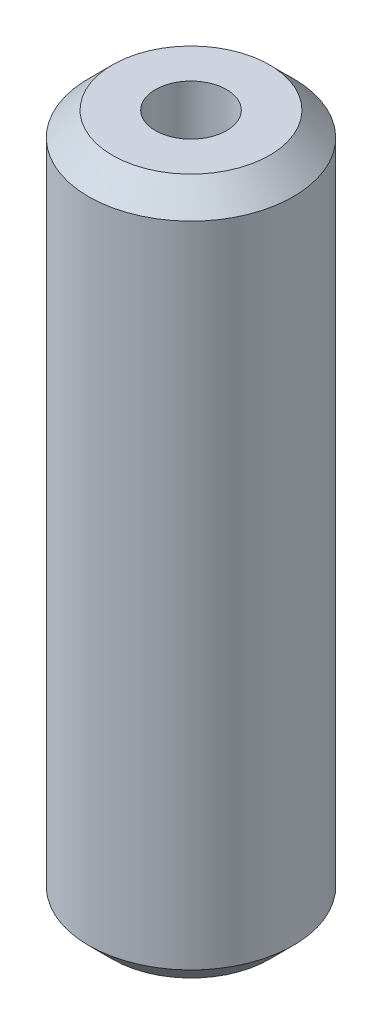
SolidWorks part; units mm, degrees
ref_plane "Front Plane" through (0, 0, 0) normal (0, 0, 1) x (1, 0, 0)
ref_plane "Top Plane" through (0, 0, 0) normal (0, 1, 0) x (1, 0, 0)
ref_plane "Right Plane" through (0, 0, 0) normal (1, 0, 0) x (0, 0, -1)
sketch "Sketch1" plane through (0, 0, 0) normal (0, 1, 0) x (1, 0, 0)
  circle A0 centre (0, 0) radius 20
  dimension "SHAFT_OD" = 40
extrude "Boss-Extrude1" add sketch "Sketch1" along normal blind 136.0494
sketch "Sketch2" plane through (0, 0, 0) normal (0, 1, 0) x (1, 0, 0)
  circle A0 centre (0, 0) radius 6.9582
  dimension "BORE_D" = 13.9164
extrude "Cut-Extrude1" cut sketch "Sketch2" along normal through all
chamfer "Chamfer1" distance 4.6616 angle 45 2 edges at (0, 136.0494, 20) (0, 0, 20)
